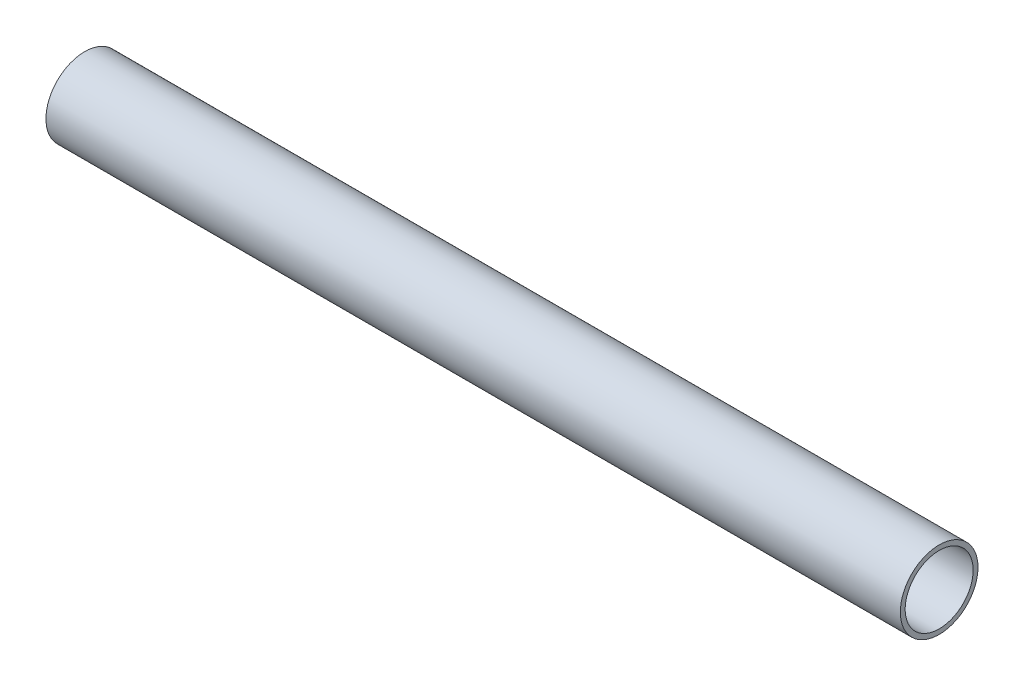
SolidWorks part; units mm, degrees
material "PC High Viscosity"
ref_plane "Front Plane" through (0, 0, 0) normal (0, 0, 1) x (1, 0, 0)
ref_plane "Top Plane" through (0, 0, 0) normal (0, 1, 0) x (1, 0, 0)
ref_plane "Right Plane" through (0, 0, 0) normal (1, 0, 0) x (0, 0, -1)
sketch "Sketch1" plane through (0, 0, 0) normal (1, 0, 0) x (0, 0, -1)
  circle A0 centre (0, 0) radius 25.4
  circle A1 centre (0, 0) radius 22.225
  dimension "D1" = 50.8
  dimension "D2" = 3.175
extrude "Boss-Extrude1" add sketch "Sketch1" along normal mid plane 558.8
